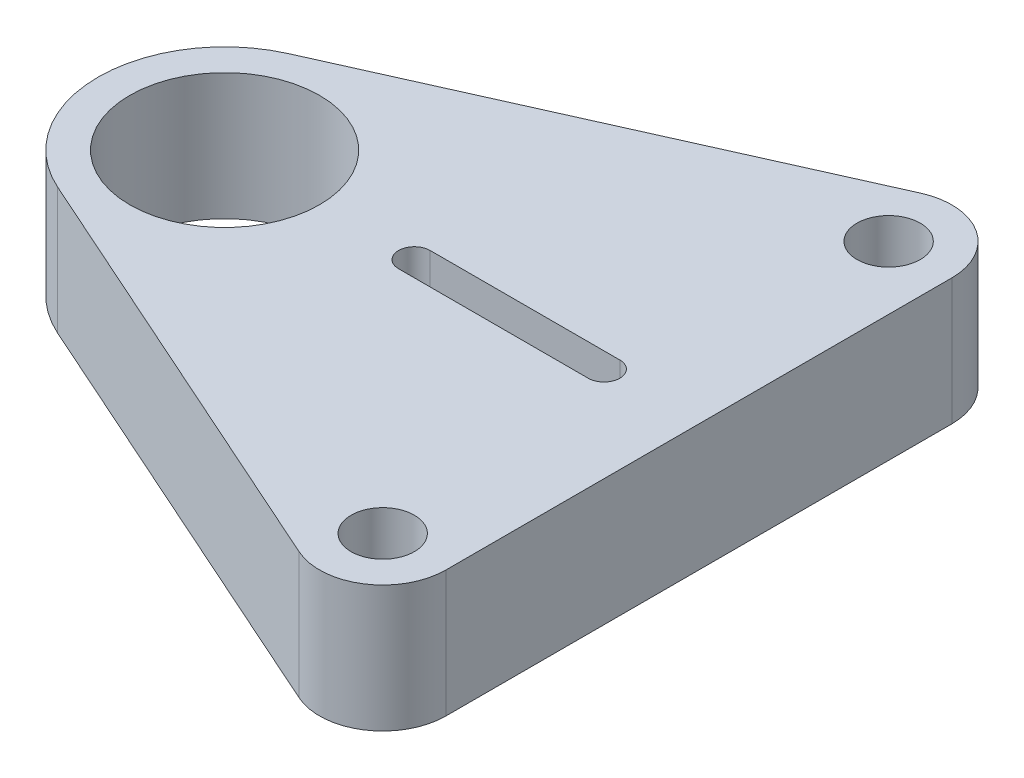
SolidWorks part; units mm, degrees
ref_plane "Alzado" through (0, 0, 0) normal (0, 0, 1) x (1, 0, 0)
ref_plane "Planta" through (0, 0, 0) normal (0, 1, 0) x (1, 0, 0)
ref_plane "Vista lateral" through (0, 0, 0) normal (1, 0, 0) x (0, 0, -1)
sketch "Sketch1" plane through (0, 0, 0) normal (0, 1, 0) x (1, 0, 0)
  line L0 (121.8402, 98.2597) -> (-16.3197, 36.5194)
  line L1 (-16.3197, -36.5194) -> (121.8402, -98.2597)
  line L3 (60, -5) -> (120, -5)
  line L4 (150, -80) -> (150, 80)
  line L6 (60, 5) -> (120, 5)
  arc A0 (-16.3197, 36.5194) -> (-16.3197, -36.5194) centre (0, 0) ccw
  circle A1 centre (0, 0) radius 30
  arc A2 (150, 80) -> (121.8402, 98.2597) centre (130, 80) ccw
  circle A3 centre (130, 80) radius 10
  arc A4 (121.8402, -98.2597) -> (150, -80) centre (130, -80) ccw
  circle A5 centre (130, -80) radius 10
  arc A6 (60, 5) -> (60, -5) centre (60, 0) ccw
  arc A7 (120, -5) -> (120, 5) centre (120, 0) ccw
  point P19 (0, 0)
  point P20 (0, 0)
  dimension "D1" = 20
  dimension "D3" = 20
  dimension "D4" = 20
  dimension "D5" = 20
  dimension "D8" = 40
  dimension "D9" = 60
  dimension "D10" = 10
  dimension "D2" = 160
  dimension "D6" = 130
  dimension "D7" = 80
  dimension "D11" = 60
  dimension "D12" = 30
extrude "Boss-Extrude1" add sketch "Sketch1" along normal blind 20 and the other way blind 20
